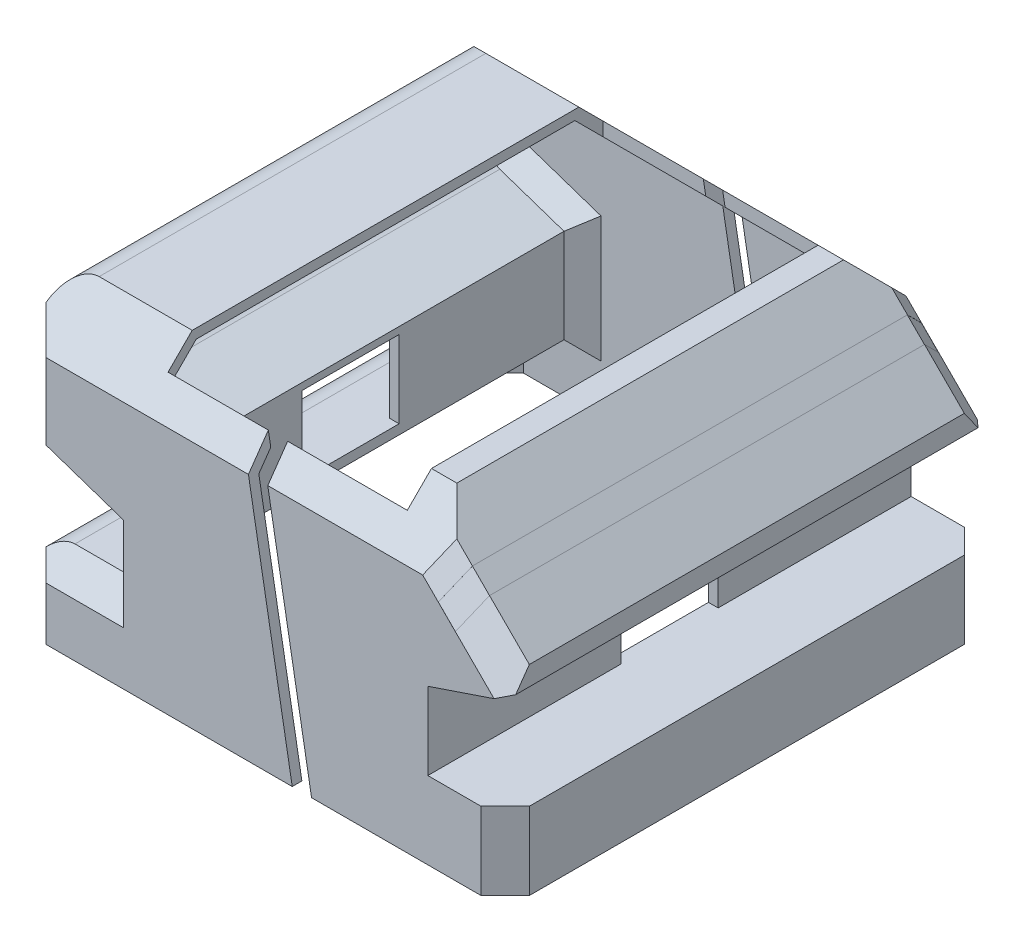
SolidWorks part; units mm, degrees
ref_plane "Alzado" through (0, 0, 0) normal (0, 0, 1) x (1, 0, 0)
ref_plane "Planta" through (0, 0, 0) normal (0, 1, 0) x (1, 0, 0)
ref_plane "Vista lateral" through (0, 0, 0) normal (1, 0, 0) x (0, 0, -1)
sketch "Croquis1" plane through (0, 0, 490) normal (0, 0, 1) x (1, 0, 0)
  line L0 (127.898, 39.7071) -> (71.653, 39.7071) construction
  line L1 (-302.102, 39.7071) -> (197.898, 39.7071)
  line L2 (-302.102, 39.7071) -> (-302.102, 119.7071)
  line L3 (-302.102, 346.7071) -> (97.898, 346.7071)
  line L5 (-277.102, 41.7071) -> (-277.102, 49.9571) construction
  line L10 (197.898, 39.7071) -> (197.898, 119.7071)
  line L11 (-302.102, 119.7071) -> (-222.102, 119.7071)
  line L13 (172.898, 49.9571) -> (172.898, 41.7071) construction
  line L15 (-222.102, 119.7071) -> (-222.102, 199.7071)
  line L16 (-222.102, 199.7071) -> (-302.102, 226.7071)
  line L17 (-302.102, 226.7071) -> (-302.102, 346.7071)
  line L18 (197.898, 246.7071) -> (97.898, 346.7071)
  line L19 (-145.852, 316.7071) -> (-170.852, 316.7071) construction
  line L21 (-52.102, 39.7071) -> (-52.102, 346.7071) construction
  line L22 (197.898, 119.7071) -> (117.898, 119.7071)
  line L23 (117.898, 119.7071) -> (117.898, 199.7071)
  line L24 (117.898, 199.7071) -> (197.898, 226.7071)
  line L25 (197.898, 226.7071) -> (197.898, 246.7071)
  dimension "D1" = 25
  dimension "D2" = 25
  dimension "D3" = 80
  dimension "D4" = 120
  dimension "D5" = 30
  dimension "D7" = 80
  dimension "D8" = 100
  dimension "D9" = 45
  dimension "D10" = 80
extrude "Saliente-Extruir1" add sketch "Croquis1" against normal offset from surface (500 mm away) 25 from offset 25 offset beyond the face yes
chamfer "Chaflán2" distance 25 angle 45 13 edges at (197.898, 79.7071, 515) (197.898, 79.7071, 15) (-302.102, 79.7071, 15) (-262.102, 119.7071, 15) (-222.102, 159.7071, 15) (-262.102, 213.2071, 15) (-302.102, 286.7071, 15) (147.898, 296.7071, 15) (-302.102, 79.7071, 515) (-262.102, 119.7071, 515) (-222.102, 159.7071, 515) (-302.102, 286.7071, 515) (147.898, 296.7071, 515)
chamfer "Chaflán3" distance 50 angle 45 2 edges at (-107.2797, 346.7071, 515) (-107.2797, 346.7071, 15)
fillet "Redondeo3" radius 30 3 edges at (-302.102, 119.7071, 265) (-302.102, 226.7071, 265) (-302.102, 346.7071, 265)
shell "Vaciado1" thickness 10 removed face at (-52.102, 39.7071, 265)
sketch "Croquis4" plane through (0, 346.7071, 0) normal (0, 1, 0) x (1, 0, 0)
  line L0 (-175.852, -490) -> (-175.852, -40) construction
  line L1 (-175.852, -490) -> (-175.852, -40)
  line L2 (71.653, -490) -> (71.653, -40) construction
  line L3 (71.653, -490) -> (71.653, -40)
  line L4 (-175.852, -40) -> (71.653, -40)
  line L5 (-175.852, -490) -> (71.653, -490)
extrude "Cortar-Extruir1" cut sketch "Croquis4" against normal up to next
sketch "Croquis5" plane through (0, 0, 15) normal (0, 0, -1) x (-1, 0, 0)
  line L0 (52.0995, 321.7071) -> (2.3753, 39.7071)
  line L1 (175.852, 321.7071) -> (-71.653, 321.7071) construction
  line L3 (-172.898, 39.7071) -> (277.102, 39.7071) construction
  line L4 (72.0995, 321.7071) -> (22.3753, 39.7071)
  line L5 (175.852, 321.7071) -> (-71.653, 321.7071) construction
  line L6 (52.0995, 321.7071) -> (72.0995, 321.7071)
  line L7 (2.3753, 39.7071) -> (22.3753, 39.7071)
  point P15 (52.0995, 321.7071)
  dimension "D1" = 20
  dimension "D2" = 80
extrude "Cortar-Extruir2" cut sketch "Croquis5" against normal through all
sketch "Croquis6" plane through (-302.102, 0, 0) normal (-1, 0, 0) x (0, 0, 1)
  line L0 (122.5, 307.4759) -> (127.5, 312.4759)
  line L1 (127.5, 252.4759) -> (177.5, 252.4759)
  line L2 (122.5, 257.4759) -> (122.5, 267.4759)
  line L3 (127.5, 312.4759) -> (177.5, 312.4759)
  line L4 (137.5, 302.4759) -> (167.5, 302.4759)
  line L5 (132.5, 297.4759) -> (132.5, 272.4759)
  line L6 (137.5, 262.4759) -> (167.5, 262.4759)
  line L7 (172.5, 292.4759) -> (172.5, 267.4759)
  line L8 (377.5, 252.4759) -> (377.5, 312.4759) construction
  line L9 (182.5, 282.4759) -> (122.5, 282.4759) construction
  line L10 (152.5, 252.4759) -> (152.5, 312.4759) construction
  line L11 (182.5, 307.4759) -> (177.5, 312.4759)
  line L12 (182.5, 257.4759) -> (177.5, 252.4759)
  line L13 (122.5, 257.4759) -> (127.5, 252.4759)
  line L14 (182.5, 307.4759) -> (182.5, 297.4759)
  line L15 (172.5, 297.4759) -> (182.5, 297.4759)
  line L16 (172.5, 292.4759) -> (182.5, 292.4759)
  line L17 (132.5, 267.4759) -> (122.5, 267.4759)
  line L18 (132.5, 272.4759) -> (122.5, 272.4759)
  line L19 (122.5, 272.4759) -> (122.5, 307.4759)
  line L20 (182.5, 292.4759) -> (182.5, 257.4759)
  line L21 (265, 316.7071) -> (265, 208.7482) construction
  line L22 (265, 282.4759) -> (40, 282.4759) construction
  line L23 (347.5, 282.4759) -> (407.5, 282.4759) construction
  line L24 (347.5, 292.4759) -> (347.5, 257.4759)
  line L25 (407.5, 272.4759) -> (407.5, 307.4759)
  line L26 (397.5, 272.4759) -> (407.5, 272.4759)
  line L27 (397.5, 267.4759) -> (407.5, 267.4759)
  line L28 (357.5, 292.4759) -> (347.5, 292.4759)
  line L29 (357.5, 297.4759) -> (347.5, 297.4759)
  line L30 (347.5, 307.4759) -> (347.5, 297.4759)
  line L31 (407.5, 257.4759) -> (402.5, 252.4759)
  line L32 (347.5, 257.4759) -> (352.5, 252.4759)
  line L33 (347.5, 307.4759) -> (352.5, 312.4759)
  line L34 (357.5, 292.4759) -> (357.5, 267.4759)
  line L35 (392.5, 262.4759) -> (362.5, 262.4759)
  line L36 (397.5, 297.4759) -> (397.5, 272.4759)
  line L37 (392.5, 302.4759) -> (362.5, 302.4759)
  line L38 (402.5, 312.4759) -> (352.5, 312.4759)
  line L39 (407.5, 257.4759) -> (407.5, 267.4759)
  line L40 (402.5, 252.4759) -> (352.5, 252.4759)
  line L41 (407.5, 307.4759) -> (402.5, 312.4759)
  line L42 (490, 316.7071) -> (40, 316.7071) construction
  line L44 (40, 316.7071) -> (40, 248.2447) construction
  arc A0 (137.5, 262.4759) -> (132.5, 267.4759) centre (137.5, 267.4759) cw
  arc A1 (172.5, 267.4759) -> (167.5, 262.4759) centre (167.5, 267.4759) cw
  arc A2 (167.5, 302.4759) -> (172.5, 297.4759) centre (167.5, 297.4759) cw
  arc A3 (137.5, 302.4759) -> (132.5, 297.4759) centre (137.5, 297.4759) ccw
  arc A4 (392.5, 302.4759) -> (397.5, 297.4759) centre (392.5, 297.4759) cw
  arc A5 (362.5, 302.4759) -> (357.5, 297.4759) centre (362.5, 297.4759) ccw
  arc A6 (357.5, 267.4759) -> (362.5, 262.4759) centre (362.5, 267.4759) ccw
  arc A7 (392.5, 262.4759) -> (397.5, 267.4759) centre (392.5, 267.4759) ccw
  point P8 (152.5, 252.4759)
  point P9 (152.5, 302.4759)
  point P35 (152.5, 282.4759)
  point P36 (152.5, 282.4759)
  point P72 (265, 316.7071)
  dimension "D7" = 5
  dimension "D1" = 10
  dimension "D2" = 10
  dimension "D3" = 45
  dimension "D4" = 5
  dimension "D5" = 60
  dimension "D6" = 10
  dimension "D8" = 5
  dimension "D9" = 5
  dimension "D10" = 60
extrude "Cortar-Extruir3" cut sketch "Croquis6" against normal blind 0.1
sketch "Croquis8" plane through (222.3026, 222.3026, 0) normal (0.7071, 0.7071, 0) x (0, 0, -1)
  line L0 (-265, 175.9347) -> (-265, 34.5133) construction
  line L1 (-490, 117.724) -> (-40, 117.724)
  line L2 (-490, 117.724) -> (-490, 92.724)
  line L3 (-490, 92.724) -> (-40, 92.724)
  line L4 (-40, 117.724) -> (-40, 92.724)
  line L5 (-65, 175.9347) -> (-465, 175.9347) construction
  line L6 (-40, 34.5133) -> (-490, 34.5133) construction
  line L7 (-40, 34.5133) -> (-40, 140.5793) construction
  point P6 (-265, 105.224)
  point P7 (-490, 105.224)
  point P8 (-265, 117.724)
  dimension "D2" = 25
extrude "Cortar-Extruir4" cut sketch "Croquis8" against normal blind 0.1
sketch "Croquis9" plane through (97.0091, 97.0091, -137.1916) normal (0.5, 0.5, -0.7071) x (-0.866, 0.2887, -0.4082)
  line L0 (-36.5978, 237.7251) -> (-48.5551, 272.5713)
  line L1 (-57.0102, 223.2913) -> (-36.5978, 237.7251)
  line L2 (-17.9365, 250.9206) -> (-103.2397, 190.6022) construction
  line L3 (-17.9365, 250.9206) -> (-29.8938, 285.7668) construction
  line L4 (-57.0102, 223.2913) -> (-68.9676, 258.1375)
  line L5 (-48.5551, 272.5713) -> (-68.9676, 258.1375)
extrude "Cortar-Extruir5" cut sketch "Croquis9" against normal blind 0.1
sketch "Croquis10" plane through (284.3924, 284.3924, 402.1916) normal (0.5, 0.5, 0.7071) x (0.866, -0.2887, -0.4082)
  line L0 (-167.8164, -33.4244) -> (-179.7738, -68.2706)
  line L1 (-113.1319, -115.3935) -> (-198.4351, -55.075) construction
  line L2 (-147.404, -47.8581) -> (-159.3614, -82.7043)
  line L3 (-186.4778, -20.2289) -> (-198.4351, -55.075) construction
  line L4 (-167.8164, -33.4244) -> (-147.404, -47.8581)
  line L5 (-159.3614, -82.7043) -> (-179.7738, -68.2706)
extrude "Cortar-Extruir6" cut sketch "Croquis10" against normal blind 0.1
sketch "Croquis11" plane through (-302.102, 0, 0) normal (-1, 0, 0) x (0, 0, 1)
  line L0 (490, 248.2447) -> (490, 316.7071) construction
  line L1 (249.5, 297.9759) -> (280.5, 297.9759)
  line L2 (249.5, 297.9759) -> (249.5, 266.9759)
  line L3 (249.5, 266.9759) -> (280.5, 266.9759)
  line L4 (280.5, 297.9759) -> (280.5, 266.9759)
  line L5 (40, 248.2447) -> (490, 248.2447) construction
  line L6 (40, 316.7071) -> (40, 248.2447) construction
  line L7 (490, 316.7071) -> (40, 316.7071) construction
  line L8 (490, 248.2447) -> (490, 316.7071) construction
  line L9 (40, 248.2447) -> (490, 248.2447) construction
  line L10 (40, 316.7071) -> (40, 248.2447) construction
  line L11 (490, 316.7071) -> (40, 316.7071) construction
  point P8 (265, 316.7071)
  point P9 (265, 297.9759)
  point P10 (40, 282.4759)
  point P11 (249.5, 282.4759)
  dimension "D1" = 31
  dimension "D2" = 31
extrude "Cortar-Extruir7" cut sketch "Croquis11" against normal up to next
sketch "Croquis12" plane through (-222.102, 0, 0) normal (-1, 0, 0) x (0, 0, 1)
  line L0 (40, 199.7071) -> (490, 199.7071) construction
  line L1 (214.7, 199.7071) -> (315.3, 199.7071)
  line L2 (214.7, 199.7071) -> (214.7, 119.7071)
  line L3 (214.7, 119.7071) -> (315.3, 119.7071)
  line L4 (315.3, 199.7071) -> (315.3, 119.7071)
  line L5 (40, 119.7071) -> (490, 119.7071) construction
  point P8 (265, 199.7071)
  point P9 (265, 199.7071)
  dimension "D1" = 100.6
extrude "Cortar-Extruir8" cut sketch "Croquis12" against normal through all
